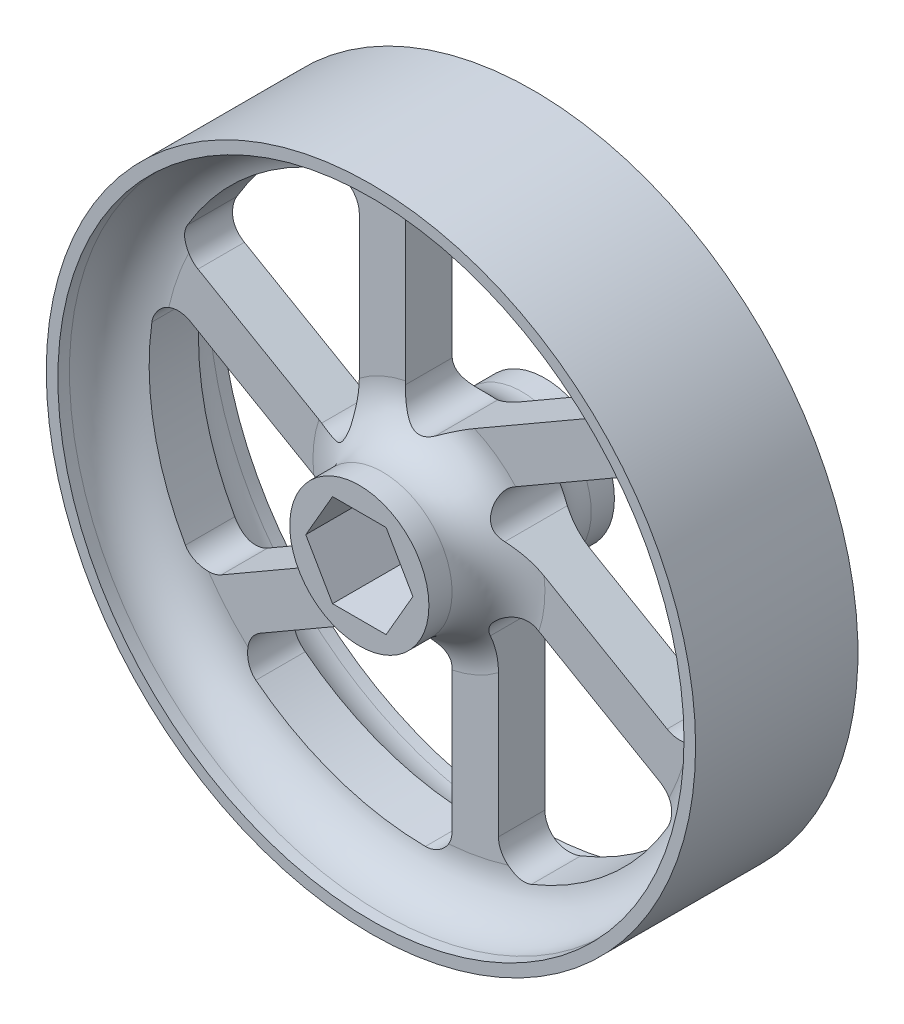
SolidWorks part; units mm, degrees
material "6061-T6 (SS)"
ref_plane "Front Plane" through (0, 0, 0) normal (0, 0, 1) x (1, 0, 0)
ref_plane "Top Plane" through (0, 0, 0) normal (0, 1, 0) x (1, 0, 0)
ref_plane "Right Plane" through (0, 0, 0) normal (1, 0, 0) x (0, 0, -1)
sketch "Sketch1" plane through (0, 0, 0) normal (0, 0, 1) x (1, 0, 0)
  line L1 (3.6662, -6.35) -> (7.3323, 0)
  line L2 (7.3323, 0) -> (3.6662, 6.35)
  line L3 (3.6662, 6.35) -> (-3.6662, 6.35)
  line L4 (-3.6662, 6.35) -> (-7.3323, 0)
  line L5 (-7.3323, 0) -> (-3.6662, -6.35)
  line L6 (-3.6662, -6.35) -> (3.6662, -6.35)
  circle A0 centre (0, 0) radius 44.45
  circle A1 centre (0, 0) radius 6.35 construction
  dimension "D1" = 88.9
  dimension "D2" = 12.7
extrude "Boss-Extrude1" add sketch "Sketch1" along normal mid plane 25.4
sketch "Sketch2" plane through (0, 0, 0) normal (0, 1, 0) x (1, 0, 0)
  line L0 (0, -1000) -> (0, 49000) construction
  line L1 (-1000, 0) -> (49000, 0) construction
  line L2 (-36.5125, 3.175) -> (-15.875, 3.175)
  line L3 (-42.8625, 9.525) -> (-42.8625, 12.7)
  line L4 (44.45, 12.7) -> (-44.45, 12.7) construction
  line L5 (-44.45, 12.7) -> (-44.45, -12.7) construction
  line L6 (-9.525, 9.525) -> (-9.525, 12.7)
  line L7 (-9.525, 12.7) -> (-42.8625, 12.7)
  arc A0 (-42.8625, 9.525) -> (-36.5125, 3.175) centre (-36.5125, 9.525) ccw
  arc A1 (-15.875, 3.175) -> (-9.525, 9.525) centre (-15.875, 9.525) ccw
  dimension "D1" = 12.7
  dimension "D2" = 6.35
  dimension "D3" = 1.5875
  dimension "D4" = 19.05
revolve "Cut-Revolve1" cut sketch "Sketch2" angle 360 about L0
mirror "Mirror1" about plane through (0, 0, 0) normal (0, 0, 1) of "Cut-Revolve1"
sketch "Sketch3" plane through (0, 0, 12.7) normal (0, 0, 1) x (1, 0, 0)
  circle A0 centre (0, 0) radius 27.1324
extrude "Cut-Extrude1" cut sketch "Sketch3" against normal blind 1.5875 flip side to cut
mirror "Mirror2" about plane through (0, 0, 0) normal (0, 0, 1) of "Cut-Extrude1"
sketch "Sketch4" plane through (0, 0, 3.175) normal (0, 0, 1) x (1, 0, 0)
  line L0 (-9.525, 0) -> (-9.525, 36.8902) construction
  line L1 (-3.175, 15.1046) -> (-3.175, 34.6701)
  line L2 (1.9685, 12.135) -> (23.089, 24.3289)
  arc A0 (23.4884, 29.9984) -> (0.2791, 38.099) centre (0, 0) ccw
  circle A1 centre (0, 0) radius 9.525 construction
  arc A2 (1.9685, 12.135) -> (-3.175, 15.1046) centre (0.254, 15.1046) cw
  circle A3 centre (0, 0) radius 9.525 construction
  circle A4 centre (0, 0) radius 44.45 construction
  arc A5 (23.089, 24.3289) -> (23.4884, 29.9984) centre (21.3745, 27.2985) ccw
  arc A6 (-3.175, 34.6701) -> (0.2791, 38.099) centre (0.254, 34.6701) cw
  point P2 (-3.175, 8.9803)
  point P12 (0, 0)
  point P13 (31.7098, 23.7181)
  point P14 (36.6381, 9.3924)
  dimension "D4" = 6.35
  dimension "D2" = 3.429
  dimension "D1" = 6.35
  dimension "D3" = 60
extrude "Cut-Extrude2" cut sketch "Sketch4" against normal through all both and the other way through all
pattern_circular "CirPattern1" count 6 over 360 about axis through (0, 0, -1000) along (0, 0, -1) of "Cut-Extrude2"
